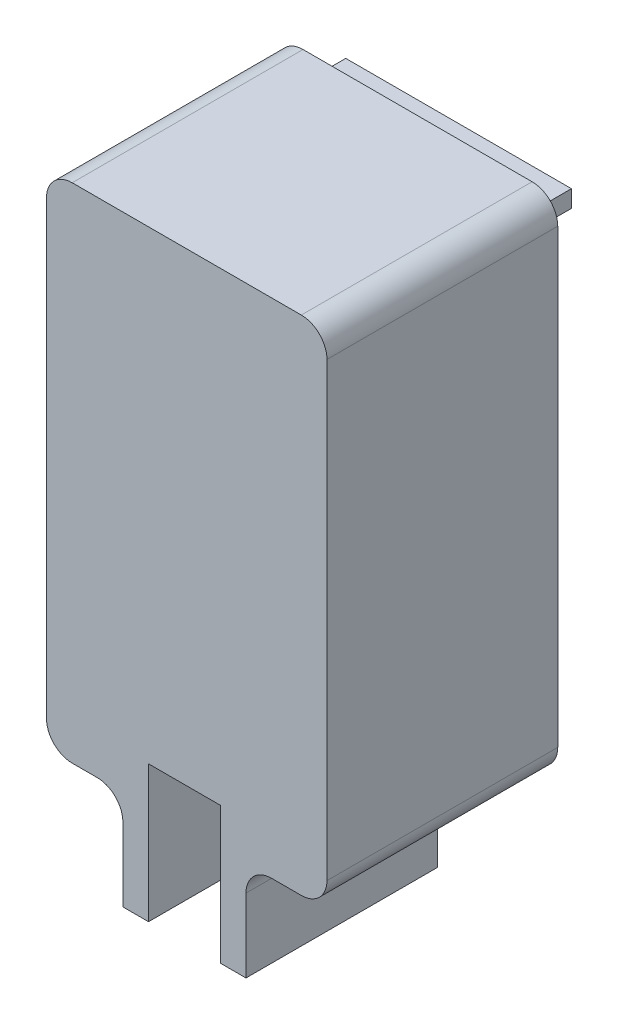
SolidWorks part; units mm, degrees
ref_plane "Front Plane" through (0, 0, 0) normal (0, 0, 1) x (1, 0, 0)
ref_plane "Top Plane" through (0, 0, 0) normal (0, 1, 0) x (1, 0, 0)
ref_plane "Right Plane" through (0, 0, 0) normal (1, 0, 0) x (0, 0, -1)
sketch "Sketch1" plane through (0, 0, 0) normal (0, 0, 1) x (1, 0, 0)
  line L0 (-6, 13.5) -> (-6, -13.5)
  line L1 (7.2, 13.5) -> (-7.2, 13.5)
  line L2 (7.2, 13.5) -> (7.2, -13.5)
  line L3 (7.2, -13.5) -> (-7.2, -13.5)
  line L4 (-7.2, 13.5) -> (-7.2, -13.5)
  line L5 (7.2, 13.5) -> (-7.2, -13.5) construction
  line L6 (7.2, -13.5) -> (-7.2, 13.5) construction
  line L7 (6, 12.5) -> (-6, 12.5)
  line L8 (6, 12.5) -> (6, -12.5)
  line L9 (6, -12.5) -> (-6, -12.5)
  line L10 (-6, 12.5) -> (-6, -12.5)
  line L11 (6, 12.5) -> (-6, -12.5) construction
  line L12 (6, -12.5) -> (-6, 12.5) construction
  line L13 (6, -12.5) -> (7.2, -12.5)
  line L14 (6, 12.5) -> (7.2, 12.5)
  line L15 (-7, 13.5) -> (-7, -13.5)
  point P0 (0, 0)
  point P6 (0, 0)
  dimension "D1" = 1
  dimension "D2" = 14.4
  dimension "D3" = 12
  dimension "D4" = 25
  dimension "D5" = 1
extrude "Boss-Extrude1" add sketch "Sketch1" along normal blind 14 contours L7 L14 L2 L1 L0 | L13 L9 L0 L3 L2 region at (0.6, 13, 0) region at (0.6, -13, 0)
extrude "Boss-Extrude2" add sketch "Sketch1<3>" along normal up to surface (14 mm away) from offset 2 contours L1 L15 L3 L0 | L14 L8 L13 L2 region at (-6.5, 0, 0) region at (6.6, 0, 0) up to face at (0.6, 13, 14)
sketch "Sketch1<3>" plane through (0, 0, 0) normal (0, 0, 1) x (1, 0, 0) same geometry as "Sketch1"
sketch "Sketch2" plane through (0, 0, 14) normal (0, 0, 1) x (1, 0, 0)
  line L0 (7.2, 13.5) -> (7.2, -13.5) construction
  line L1 (7, 13.5) -> (-7, 13.5)
  line L3 (7, -13.5) -> (-7, -13.5)
  line L4 (-7, 13.5) -> (-7, -13.5)
  line L5 (7, 13.5) -> (-7, -13.5) construction
  line L6 (7, -13.5) -> (-7, 13.5) construction
  line L7 (7.2, 13.5) -> (7.2, -13.5)
  line L8 (7.2, -13.5) -> (-7, -13.5) construction
  line L9 (7.2, -13.5) -> (-7, -13.5)
  line L10 (7.2, 13.5) -> (-7, 13.5) construction
  line L11 (7.2, 13.5) -> (-7, 13.5)
  point P0 (0, 0)
  line M5 (-6, 12.5) -> (6, 12.5)
  line M6 (6, 12.5) -> (6, -12.5)
  line M7 (6, -12.5) -> (-6, -12.5)
  line M8 (-6, -12.5) -> (-6, 12.5)
  line M9 (-7, -13.5) -> (7.2, -13.5)
  line M10 (7.2, -13.5) -> (7.2, 13.5)
  line M11 (7.2, 13.5) -> (-7, 13.5)
  line M12 (-7, 13.5) -> (-7, -13.5)
extrude "Boss-Extrude3" add sketch "Sketch2" along normal blind 1.5 contours M5 M8 M7 M6 | M12 M9 M10 M11 M8 M5 M6 M7 region at (7.1, 13.1949, 14) region at (0, 0, 14)
sketch "Sketch3" plane through (0, -13.5, 0) normal (0, -1, 0) x (1, 0, 0)
  line L0 (0.1, 15.5) -> (0, 0) construction
  line L1 (-7, 15.5) -> (7.2, 15.5) construction
  line L2 (2.1639, 14) -> (2.1639, 15.5)
  line L3 (2.1639, 14) -> (-2.0361, 14)
  line L4 (2.1639, 14) -> (2.1639, 5.8)
  line L5 (2.1639, 5.8) -> (-2.0361, 5.8)
  line L6 (-2.0361, 14) -> (-2.0361, 5.8)
  line L7 (2.1639, 14) -> (-2.0361, 5.8) construction
  line L8 (2.1639, 5.8) -> (-2.0361, 14) construction
  line L9 (2.1639, 15.5) -> (-2.0361, 15.5)
  line L10 (-2.0361, 15.5) -> (-2.0361, 14)
  point P5 (0.0639, 9.9)
  line M10 (7.2, 15.5) -> (-7, 15.5)
  dimension "D1" = 1.5
  dimension "D2" = 8.2
  dimension "D3" = 4.2
extrude "Cut-Extrude1" cut sketch "Sketch3" against normal up to surface (1 mm away) contours L3 L6 L5 L4 | L10 L3 L2 M10 region at (0.0639, -13.5, 14.75) region at (0.0639, -13.5, 9.9) up to face at (1.2, -12.5, 4.8571)
sketch "Sketch4" plane through (0, -13.5, 0) normal (0, -1, 0) x (1, 0, 0)
  line L0 (2.1639, 10.65) -> (-2.0361, 10.65) construction
  line L1 (2.1639, 15.5) -> (2.1639, 5.8) construction
  line L2 (-2.0361, 15.5) -> (-2.0361, 5.8) construction
  line L3 (2.1639, 5.8) -> (-2.0361, 5.8) construction
  line L4 (2.1639, 15.5) -> (-2.0361, 15.5)
  line L5 (2.1639, 15.5) -> (2.1639, 5.8)
  line L6 (2.1639, 5.8) -> (-2.0361, 5.8)
  line L7 (-2.0361, 15.5) -> (-2.0361, 5.8)
  line L8 (2.1639, 15.5) -> (-2.0361, 5.8) construction
  line L9 (2.1639, 5.8) -> (-2.0361, 15.5) construction
  line L10 (-7, 15.5) -> (3.6639, 15.5)
  line L11 (3.6639, 17) -> (-3.5361, 17)
  line L12 (3.6639, 17) -> (3.6639, 4.3)
  line L13 (3.6639, 4.3) -> (-3.5361, 4.3)
  line L14 (-3.5361, 17) -> (-3.5361, 4.3)
  line L15 (3.6639, 17) -> (-3.5361, 4.3) construction
  line L16 (3.6639, 4.3) -> (-3.5361, 17) construction
  point P6 (0.0639, 10.65)
  point P13 (0.0639, 10.65)
  line M10 (-2.0361, 5.8) -> (-2.0361, 15.5)
  line M11 (-2.0361, 15.5) -> (-7, 15.5)
  line M17 (7.2, 15.5) -> (2.1639, 15.5)
  line M18 (2.1639, 15.5) -> (2.1639, 5.8)
  line M19 (2.1639, 5.8) -> (-2.0361, 5.8)
  dimension "D1" = 1.5
  dimension "D2" = 1.5
extrude "Boss-Extrude4" add sketch "Sketch4" along normal blind 7 contours L14 L13 L12 M11 M17 M18 M19 M10 region at (2.9139, -13.5, 15.3669)
fillet "Fillet2" radius 2 4 edges at (-6, -12.5, 8) (-6, 12.5, 8) (6, 12.5, 8) (6, -12.5, 8)
sketch "Sketch5" plane through (0, 0, 2) normal (0, 0, -1) x (-1, 0, 0)
  line L0 (-7.2, -12.5) -> (6, -12.5)
  line L1 (6, -12.5) -> (6, -13.5)
  line L2 (6, -13.5) -> (-7.2, -13.5)
  line L3 (-7.2, -13.5) -> (-7.2, -12.5)
extrude "Cut-Extrude2" cut sketch "Sketch5" along normal up to surface (2 mm away) up to face at (0.6, -13, 0)
fillet "Fillet4" radius 1 3 edges at (0.0639, -13.5, 4.3) (3.6639, -13.5, 9.9) (-3.5361, -13.5, 9.9)
sketch "Sketch8" plane through (0, 0, 15.5) normal (0, 0, 1) x (1, 0, 0)
  line L0 (-7, 13.5) -> (-7, -13.5) construction
  line L1 (8.4, 14.7) -> (-8.4, 14.7)
  line L2 (8.4, 14.7) -> (8.4, -14.7)
  line L3 (8.4, -14.7) -> (-8.4, -14.7)
  line L4 (-8.4, 14.7) -> (-8.4, -14.7)
  line L5 (8.4, 14.7) -> (-8.4, -14.7) construction
  line L6 (8.4, -14.7) -> (-8.4, 14.7) construction
  line L7 (-7, 13.5) -> (-7, -13.5)
  line L8 (7.2, 13.5) -> (-7, 13.5) construction
  line L9 (7.2, 13.5) -> (-7, 13.5)
  line L10 (7.2, -13.5) -> (7.2, 13.5) construction
  line L11 (7.2, -13.5) -> (7.2, 13.5)
  line L12 (4.6639, -13.5) -> (7.2, -13.5) construction
  line L13 (4.6639, -13.5) -> (7.2, -13.5)
  line L14 (-7, -13.5) -> (-4.5361, -13.5) construction
  line L15 (-7, -13.5) -> (-4.5361, -13.5)
  arc A0 (-3.5361, -14.5) -> (-4.5361, -13.5) centre (-4.5361, -14.5) ccw construction
  arc A1 (-3.5361, -14.5) -> (-4.5361, -13.5) centre (-4.5361, -14.5) ccw
  arc A2 (4.6639, -13.5) -> (3.6639, -14.5) centre (4.6639, -14.5) ccw construction
  arc A3 (4.6639, -13.5) -> (3.6639, -14.5) centre (4.6639, -14.5) ccw
  point P0 (0, 0)
  line M11 (3.6639, -20.5) -> (3.6639, -14.5)
  arc M12 (3.6639, -14.5) -> (4.6639, -13.5) centre (4.6639, -14.5) cw
  line M13 (4.6639, -13.5) -> (7.2, -13.5)
  line M14 (7.2, -13.5) -> (7.2, 13.5)
  line M15 (7.2, 13.5) -> (-7, 13.5)
  line M16 (-7, 13.5) -> (-7, -13.5)
  line M17 (-7, -13.5) -> (-4.5361, -13.5)
  arc M18 (-4.5361, -13.5) -> (-3.5361, -14.5) centre (-4.5361, -14.5) cw
  line M19 (-3.5361, -14.5) -> (-3.5361, -20.5)
  dimension "D1" = 1.2
  dimension "D2" = 1.2
extrude "Boss-Extrude7" add sketch "Sketch8" against normal up to surface (13.5 mm away) contours L1 L4 L3 L2 M19 M18 M17 M16 M15 M14 M13 M12 M11 region at (8.0614, 0, 15.5) up to face at (-0.8286, 1.7857, 2)
sketch "Sketch9" plane through (0, 0, 2) normal (0, 0, -1) x (-1, 0, 0)
  line L0 (-5.008, -14.7) -> (5.6705, -14.7)
  line L1 (-3.6639, -14.7) -> (-8.4, -14.7) construction
  line L2 (8.4, -14.7) -> (3.5361, -14.7) construction
  line L3 (5.6705, -14.7) -> (5.6705, -12.839)
  line L4 (5.6705, -12.839) -> (-4.7971, -12.839)
  line L5 (-4.7971, -12.839) -> (-5.008, -14.7)
extrude "Boss-Extrude8" add sketch "Sketch9" against normal up to surface (2.3 mm away) up to face at (0.0639, -16.5667, 4.3)
fillet "Fillet5" radius 1.5 3 edges at (3.6639, -14.7, 9.9) (-3.5361, -14.7, 9.9) (0.0639, -14.7, 4.3)
sketch "Sketch10" plane through (0, 0, 2) normal (0, 0, -1) x (-1, 0, 0)
  line L0 (8.4, 14.7) -> (8, 14.7)
  line L1 (8.4, 14.7) -> (-8.4, 14.7) construction
  line L2 (8, 14.7) -> (8, -14.7)
  line L3 (8.4, -14.7) -> (-8.4, -14.7) construction
  line L4 (8, -14.7) -> (8.4, -14.7)
  line L5 (8.4, -14.7) -> (8.4, 14.7)
  dimension "D1" = 0.4
extrude "Cut-Extrude3" cut sketch "Sketch10" against normal up to surface (13.5 mm away) up to face at (0.0456, -12.0128, 15.5)
fillet "Fillet6" radius 1.5 4 edges at (8.4, 14.7, 8.75) (-8, 14.7, 8.75) (8.4, -14.7, 8.75) (-8, -14.7, 8.75)
